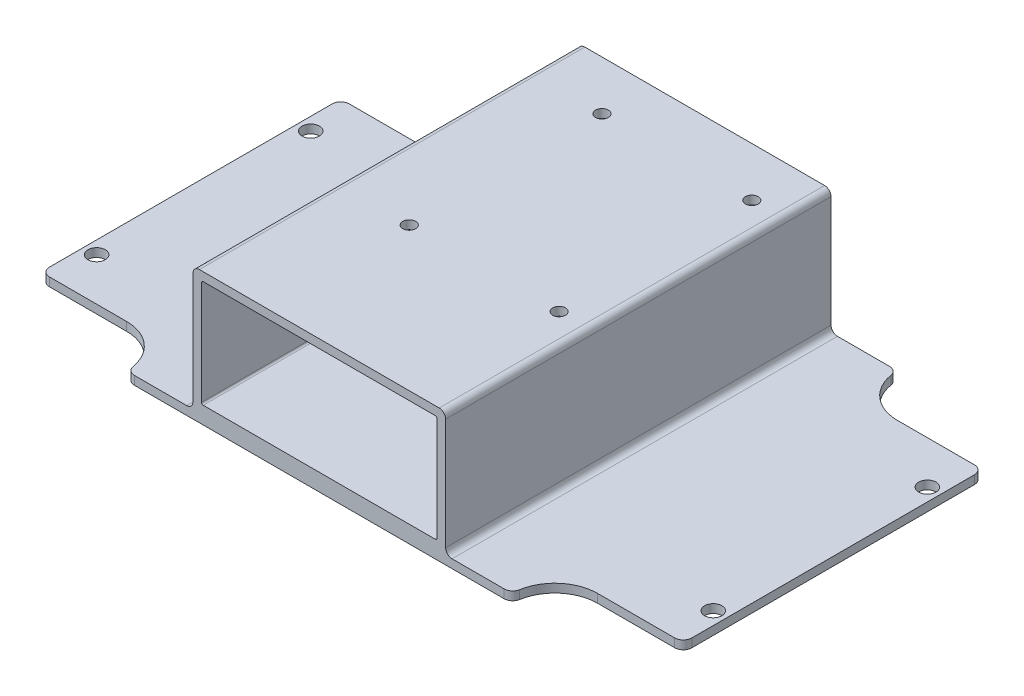
SolidWorks part; units mm, degrees
ref_plane "Front Plane" through (0, 0, 0) normal (0, 0, 1) x (1, 0, 0)
ref_plane "Top Plane" through (0, 0, 0) normal (0, 1, 0) x (1, 0, 0)
ref_plane "Right Plane" through (0, 0, 0) normal (1, 0, 0) x (0, 0, -1)
sketch "Sketch1" plane through (0, 0, 0) normal (0, 1, 0) x (1, 0, 0)
  line L0 (0, 35) -> (0, -35) construction
  line L1 (75, -35) -> (-75, -35)
  line L2 (75, -35) -> (75, 35)
  line L3 (75, 35) -> (-75, 35)
  line L4 (-75, -35) -> (-75, 35)
  line L6 (45, -45) -> (-45, -45)
  line L7 (72, -25) -> (-72, -25) construction
  line L8 (72, -25) -> (72, 25) construction
  line L9 (72, 25) -> (-72, 25) construction
  line L10 (-72, -25) -> (-72, 25) construction
  line L11 (45, -45) -> (45, 45)
  line L12 (45, 45) -> (-45, 45)
  line L13 (-75, 0) -> (75, 0) construction
  line L14 (75, -35) -> (45, -35) construction
  line L15 (-75, 35) -> (-45, 35) construction
  line L16 (-75, 35) -> (-75, -35) construction
  line L17 (-75, -35) -> (-45, -35) construction
  line L18 (-45, 35) -> (-45, -35) construction
  line L19 (-60, -35) -> (-60, 35) construction
  line L20 (-75, 0) -> (-45, 0) construction
  line L21 (45, 35) -> (45, -35) construction
  line L22 (75, 35) -> (45, 35) construction
  line L23 (75, 35) -> (75, -35) construction
  line L24 (75, 0) -> (45, 0) construction
  line L25 (60, -35) -> (60, 35) construction
  line L26 (-45, -45) -> (-45, 45)
  line L27 (45, -45) -> (-45, 45) construction
  line L28 (45, 45) -> (-45, -45) construction
  circle A0 centre (72, 25) radius 2.025
  circle A1 centre (-72, 25) radius 2.025
  circle A2 centre (-72, -25) radius 2.025
  circle A3 centre (72, -25) radius 2.025
  point P0 (0, 0)
  point P5 (0, 0)
  point P24 (60, 0)
  point P30 (0, 0)
  point P278 (-60, 0)
  dimension "D5" = 4.05
  dimension "D6" = 70
  dimension "D1" = 70
  dimension "D2" = 150
  dimension "D3" = 50
  dimension "D4" = 144
  dimension "D7" = 30
  dimension "D8" = 90
extrude "Boss-Extrude1" add sketch "Sketch1" along normal blind 2 contours L26 L1 L11 L3 | L1 L26 L3 L4 A2 A1 | L11 L1 L2 L3 A0 A3 | L26 L6 L11 L1 | L26 L3 L11 L12 region at (59.8509, 0, 0) region at (0, 0, 40) region at (0, 0, 0) region at (-59.8509, 0, 0) region at (0, 0, -40)
sketch "Sketch2" plane through (0, 2, 0) normal (0, 1, 0) x (1, 0, 0)
  line L1 (29.5, -45) -> (-29.5, -45)
  line L2 (29.5, -45) -> (29.5, 45)
  line L3 (29.5, 45) -> (-29.5, 45)
  line L4 (-29.5, -45) -> (-29.5, 45)
  line L5 (29.5, -45) -> (-29.5, 45) construction
  line L6 (29.5, 45) -> (-29.5, -45) construction
  line L7 (45, 45) -> (-45, 45) construction
  point P0 (0, 0)
  dimension "D1" = 90
  dimension "D2" = 59
extrude "Boss-Extrude2" add sketch "Sketch2" along normal blind 29
sketch "Sketch4" plane through (0, 0, 45) normal (0, 0, 1) x (1, 0, 0)
  line L1 (-29.5, 31) -> (29.5, 31)
  line L2 (-29.5, 31) -> (-29.5, 2)
  line L3 (-29.5, 2) -> (29.5, 2)
  line L4 (29.5, 31) -> (29.5, 2)
  line L5 (0, 2) -> (0, 31) construction
  line L6 (-29.5, 16.5) -> (29.5, 16.5) construction
  line L7 (27.5, 4) -> (-27.5, 4)
  line L8 (27.5, 4) -> (27.5, 29)
  line L9 (27.5, 29) -> (-27.5, 29)
  line L10 (-27.5, 4) -> (-27.5, 29)
  line L11 (27.5, 4) -> (-27.5, 29) construction
  line L12 (27.5, 29) -> (-27.5, 4) construction
  point P4 (0, 16.5)
  point P136 (0, 16.5)
  dimension "D1" = 29
  dimension "D2" = 59
  dimension "D3" = 25
  dimension "D4" = 55
extrude "Cut-Extrude1" cut sketch "Sketch4" against normal blind 87.5 contours L10 L7 L8 L9 region at (0, 16.5, 45)
fillet "Fillet1" radius 1.5 4 edges at (29.5, 31, 0) (-29.5, 2, 0) (29.5, 2, 0) (-29.5, 31, 0)
fillet "Fillet2" radius 0.4 8 edges at (27.5, 29, 1.25) (27.5, 4, 1.25) (-27.5, 4, 1.25) (-27.5, 29, 1.25) (0, 4, -42.5) (27.5, 16.5, -42.5) (-27.5, 16.5, -42.5) (0, 29, -42.5)
fillet "Fillet3" radius 10 4 edges at (-45, 1, 35) (-45, 1, -35) (45, 1, -35) (45, 1, 35)
fillet "Fillet7" radius 2 8 edges at (-45, 1, 45) (45, 1, 45) (75, 1, 35) (75, 1, -35) (45, 1, -45) (-45, 1, -45) (-75, 1, -35) (-75, 1, 35)
sketch "Sketch7" plane through (0, 31, 0) normal (0, 1, 0) x (1, 0, 0)
  line L0 (0, 0) -> (5, 0) construction
  line L1 (5, 0) -> (5, 11)
  line L2 (-14, 35) -> (-12.5, 35)
  line L3 (24, -13) -> (-14, -13)
  line L4 (24, -13) -> (24, 35)
  line L5 (24, 35) -> (-14, 35)
  line L6 (-14, -13) -> (-14, 35)
  line L7 (24, -13) -> (-14, 35) construction
  line L8 (24, 35) -> (-14, -13) construction
  line L9 (-12.5, 35) -> (-12.5, 33.5)
  line L10 (5, 35) -> (5, -13)
  line L11 (-14, 11) -> (24, 11)
  circle A0 centre (-12.5, 33.5) radius 1.5
  circle A1 centre (22.5, 33.5) radius 1.5
  circle A2 centre (22.5, -11.5) radius 1.5
  circle A3 centre (-12.5, -11.5) radius 1.5
  point P21 (0, 0)
  dimension "D1" = 48
  dimension "D3" = 3
  dimension "D2" = 38
extrude "Cut-Extrude2" cut sketch "Sketch7" against normal blind 5 contours A0 | A1 | A2 | A3 region at (22.5, 31, 11.5) region at (-12.5, 31, 11.5) region at (-11.4693, 31, -34.5307) region at (22.5, 31, -33.5)
